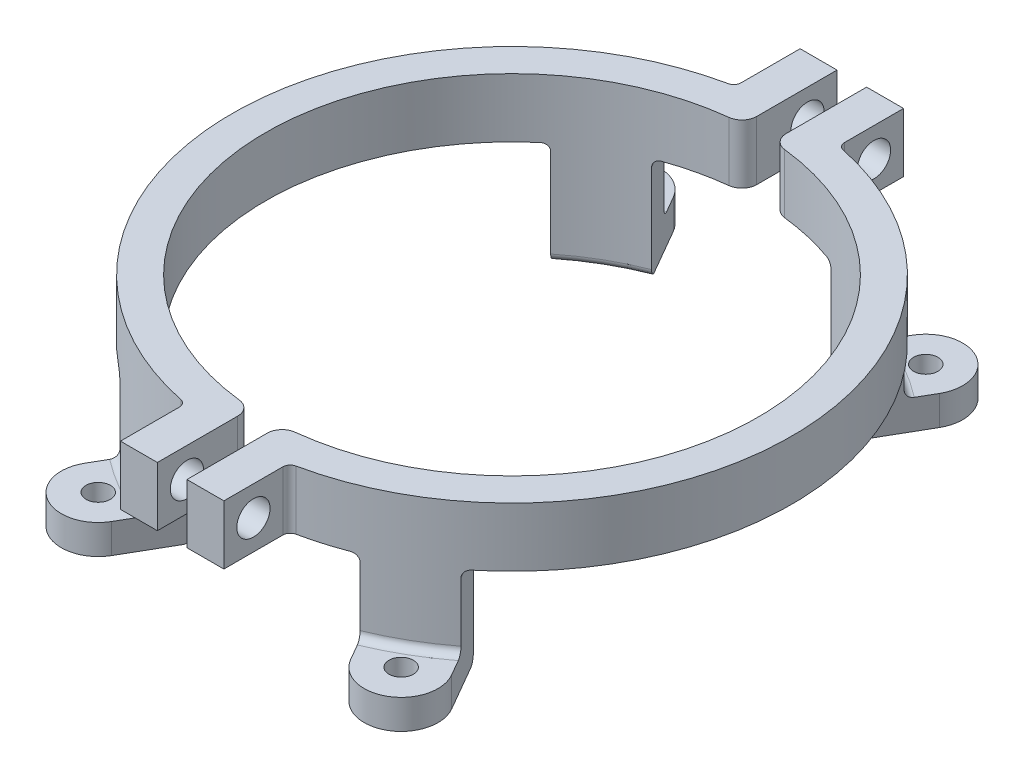
SolidWorks part; units mm, degrees
material "尼龙 101"
ref_plane "前视基准面" through (0, 0, 0) normal (0, 0, 1) x (1, 0, 0)
ref_plane "上视基准面" through (0, 0, 0) normal (0, 1, 0) x (1, 0, 0)
ref_plane "右视基准面" through (0, 0, 0) normal (1, 0, 0) x (0, 0, -1)
sketch "草图1" plane through (0, 0, 0) normal (0, 1, 0) x (1, 0, 0)
  line L0 (-7, 38.0174) -> (-7, 46)
  line L1 (-7, 46) -> (-2, 46)
  line L2 (-2, 46) -> (-2, 35.123)
  line L3 (0, 302.7374) -> (0, 0) construction
  line L4 (0, 0) -> (88.0006, 0) construction
  line L8 (2, 46) -> (2, 35.123)
  line L9 (7, 46) -> (2, 46)
  line L10 (7, 38.0174) -> (7, 46)
  line L11 (7, -38.0174) -> (7, -46)
  line L12 (7, -46) -> (2, -46)
  line L13 (2, -46) -> (2, -35.123)
  line L14 (-20.5, 35.507) -> (0, 0) construction
  line L15 (-2, -46) -> (-2, -35.123)
  line L16 (-7, -46) -> (-2, -46)
  line L17 (-7, -38.0174) -> (-7, -46)
  line L18 (-16.1699, 38.007) -> (-14.429, 34.9918)
  line L19 (-24.8301, 33.007) -> (-23.0893, 29.9918)
  line L20 (24.8301, 33.007) -> (23.0893, 29.9918)
  line L21 (16.1699, 38.007) -> (14.429, 34.9918)
  line L22 (-24.8301, -33.007) -> (-23.0893, -29.9918)
  line L23 (-16.1699, -38.007) -> (-14.429, -34.9918)
  line L24 (24.8301, -33.007) -> (23.0893, -29.9918)
  line L25 (16.1699, -38.007) -> (14.429, -34.9918)
  arc A0 (-3.7737, 33.1358) -> (-3.7737, -33.1358) centre (0, 0) ccw
  arc A1 (-23.0893, 29.9918) -> (-23.0893, -29.9918) centre (0, 0) ccw
  arc A2 (-24.8301, 33.007) -> (-16.1699, 38.007) centre (-20.5, 35.507) cw
  arc A4 (-7.7941, 37.0388) -> (-14.429, 34.9918) centre (0, 0) ccw
  arc A7 (-3.7737, 33.1358) -> (-2, 35.123) centre (-4, 35.123) ccw
  arc A8 (-7.7941, 37.0388) -> (-7, 38.0174) centre (-8, 38.0174) ccw
  arc A9 (7.7941, 37.0388) -> (7, 38.0174) centre (8, 38.0174) cw
  arc A10 (3.7737, 33.1358) -> (2, 35.123) centre (4, 35.123) cw
  arc A14 (24.8301, 33.007) -> (16.1699, 38.007) centre (20.5, 35.507) ccw
  arc A15 (14.429, 34.9918) -> (7.7941, 37.0388) centre (0, 0) ccw
  arc A16 (24.8301, -33.007) -> (16.1699, -38.007) centre (20.5, -35.507) cw
  arc A23 (-24.8301, -33.007) -> (-16.1699, -38.007) centre (-20.5, -35.507) ccw
  arc A24 (3.7737, -33.1358) -> (2, -35.123) centre (4, -35.123) ccw
  arc A25 (7.7941, -37.0388) -> (7, -38.0174) centre (8, -38.0174) ccw
  arc A26 (-7.7941, -37.0388) -> (-7, -38.0174) centre (-8, -38.0174) cw
  arc A27 (-3.7737, -33.1358) -> (-2, -35.123) centre (-4, -35.123) cw
  arc A28 (-14.429, -34.9918) -> (-7.7941, -37.0388) centre (0, 0) ccw
  arc A29 (7.7941, -37.0388) -> (14.429, -34.9918) centre (0, 0) ccw
  arc A30 (3.7737, -33.1358) -> (3.7737, 33.1358) centre (0, 0) ccw
  arc A31 (23.0893, -29.9918) -> (23.0893, 29.9918) centre (0, 0) ccw
  dimension "D1" = 66.7
  dimension "D2" = 4.5
  dimension "D6" = 5
  dimension "D10" = 1
  dimension "D12" = 2
  dimension "D3" = 4
  dimension "D4" = 5
  dimension "D8" = 41
  dimension "D9" = 60
  dimension "D11" = 92
extrude "凸台-拉伸1" add sketch "草图1" along normal mid plane 22
delete or keep bodies "实体-删除/保留 1" [suppressed] type delete bodies bodies 109
sketch "草图3" plane through (0, 11, 0) normal (0, 1, 0) x (1, 0, 0)
  line L0 (-16.1699, -38.007) -> (-14.429, -34.9918) construction
  line L1 (-23.0893, -29.9918) -> (-24.8301, -33.007) construction
  line L2 (-16.1699, -38.007) -> (-14.429, -34.9918)
  line L3 (-23.0893, -29.9918) -> (-24.8301, -33.007)
  line L4 (-11.0319, 0) -> (11.0319, 0) construction
  line L5 (-23.0893, 29.9918) -> (-24.8301, 33.007)
  line L6 (-16.1699, 38.007) -> (-14.429, 34.9918)
  line L7 (0, -11.0319) -> (0, 11.0319) construction
  line L8 (16.1699, 38.007) -> (14.429, 34.9918)
  line L9 (23.0893, 29.9918) -> (24.8301, 33.007)
  line L10 (23.0893, -29.9918) -> (24.8301, -33.007)
  line L11 (16.1699, -38.007) -> (14.429, -34.9918)
  arc A2 (-14.429, -34.9918) -> (-7.7941, -37.0388) centre (0, 0) ccw construction
  arc A3 (-23.0893, -29.9918) -> (-14.429, -34.9918) centre (0, 0) ccw
  arc A4 (-24.8301, -33.007) -> (-16.1699, -38.007) centre (-20.5, -35.507) ccw construction
  arc A6 (-24.8301, -33.007) -> (-16.1699, -38.007) centre (-20.5, -35.507) ccw
  arc A8 (-24.8301, 33.007) -> (-16.1699, 38.007) centre (-20.5, 35.507) cw
  arc A9 (-23.0893, 29.9918) -> (-14.429, 34.9918) centre (0, 0) cw
  arc A10 (23.0893, 29.9918) -> (14.429, 34.9918) centre (0, 0) ccw
  arc A11 (24.8301, 33.007) -> (16.1699, 38.007) centre (20.5, 35.507) ccw
  arc A13 (24.8301, -33.007) -> (16.1699, -38.007) centre (20.5, -35.507) cw
  arc A14 (23.0893, -29.9918) -> (14.429, -34.9918) centre (0, 0) cw
extrude "切除-拉伸2" cut sketch "草图3" against normal offset from surface (18 mm away) 4 up to face at (-13.2249, -11, 0)
sketch "草图4" plane through (0, -11, 0) normal (0, -1, 0) x (1, 0, 0)
  line L10 (0, -11.0319) -> (0, 11.0319) construction
  line L11 (20.8167, -26.0555) -> (23.0893, -29.9918)
  line L12 (23.0893, 29.9918) -> (20.8167, 26.0555)
  line L13 (12.1564, 31.0555) -> (14.429, 34.9918)
  line L14 (7, 46) -> (7, 38.0174)
  line L15 (2, 46) -> (7, 46)
  line L16 (2, 35.123) -> (2, 46)
  line L17 (2, -46) -> (2, -35.123)
  line L18 (7, -46) -> (2, -46)
  line L19 (7, -38.0174) -> (7, -46)
  line L20 (-16.1699, -38.007) -> (-14.429, -34.9918)
  line L21 (-7, -38.0174) -> (-7, -46)
  line L22 (-7, -46) -> (-2, -46)
  line L23 (-2, -46) -> (-2, -35.123)
  line L24 (-2, 35.123) -> (-2, 46)
  line L25 (-2, 46) -> (-7, 46)
  line L26 (-7, 46) -> (-7, 38.0174)
  line L27 (-14.429, 34.9918) -> (-16.1699, 38.007)
  line L28 (-24.8301, 33.007) -> (-23.0893, 29.9918)
  line L29 (-23.0893, -29.9918) -> (-24.8301, -33.007)
  line L30 (-14.429, -34.9918) -> (-12.1564, -31.0555)
  line L31 (-7, -38.0174) -> (-7, -46)
  line L32 (-7, -46) -> (-2, -46)
  line L33 (-2, -46) -> (-2, -35.123)
  line L34 (-2, 35.123) -> (-2, 46)
  line L35 (-2, 46) -> (-7, 46)
  line L36 (-7, 46) -> (-7, 38.0174)
  line L37 (-12.1564, 31.0555) -> (-14.429, 34.9918)
  line L38 (-23.0893, 29.9918) -> (-20.8167, 26.0555)
  line L39 (-20.8167, -26.0555) -> (-23.0893, -29.9918)
  line L40 (14.429, -34.9918) -> (12.1564, -31.0555)
  arc A10 (-20.8167, 26.0555) -> (-20.8167, -26.0555) centre (0, 0) ccw
  arc A11 (-12.1564, -31.0555) -> (-3.7737, -33.1358) centre (0, 0) ccw
  arc A12 (23.0893, 29.9918) -> (23.0893, -29.9918) centre (0, 0) cw
  arc A13 (7.7941, 37.0388) -> (14.429, 34.9918) centre (0, 0) cw
  arc A14 (7.7941, 37.0388) -> (7, 38.0174) centre (8, 38.0174) cw
  arc A15 (3.7737, 33.1358) -> (2, 35.123) centre (4, 35.123) cw
  arc A16 (3.7737, 33.1358) -> (12.1564, 31.0555) centre (0, 0) cw
  arc A17 (2, -35.123) -> (3.7737, -33.1358) centre (4, -35.123) cw
  arc A18 (7, -38.0174) -> (7.7941, -37.0388) centre (8, -38.0174) cw
  arc A19 (14.429, -34.9918) -> (7.7941, -37.0388) centre (0, 0) cw
  arc A20 (-24.8301, -33.007) -> (-16.1699, -38.007) centre (-20.5, -35.507) ccw
  arc A21 (-14.429, -34.9918) -> (-7.7941, -37.0388) centre (0, 0) ccw
  arc A22 (-7, -38.0174) -> (-7.7941, -37.0388) centre (-8, -38.0174) ccw
  arc A23 (-2, -35.123) -> (-3.7737, -33.1358) centre (-4, -35.123) ccw
  arc A24 (-3.7737, 33.1358) -> (-3.7737, -33.1358) centre (0, 0) ccw
  arc A25 (-3.7737, 33.1358) -> (-2, 35.123) centre (-4, 35.123) ccw
  arc A26 (-7.7941, 37.0388) -> (-7, 38.0174) centre (-8, 38.0174) ccw
  arc A27 (-7.7941, 37.0388) -> (-14.429, 34.9918) centre (0, 0) ccw
  arc A28 (-16.1699, 38.007) -> (-24.8301, 33.007) centre (-20.5, 35.507) ccw
  arc A29 (-23.0893, 29.9918) -> (-23.0893, -29.9918) centre (0, 0) ccw
  arc A31 (-14.429, -34.9918) -> (-7.7941, -37.0388) centre (0, 0) ccw
  arc A32 (-7, -38.0174) -> (-7.7941, -37.0388) centre (-8, -38.0174) ccw
  arc A33 (-2, -35.123) -> (-3.7737, -33.1358) centre (-4, -35.123) ccw
  arc A34 (-3.7737, 33.1358) -> (-12.1564, 31.0555) centre (0, 0) ccw
  arc A35 (-3.7737, 33.1358) -> (-2, 35.123) centre (-4, 35.123) ccw
  arc A36 (-7.7941, 37.0388) -> (-7, 38.0174) centre (-8, 38.0174) ccw
  arc A37 (-7.7941, 37.0388) -> (-14.429, 34.9918) centre (0, 0) ccw
  arc A39 (-23.0893, 29.9918) -> (-23.0893, -29.9918) centre (0, 0) ccw
  arc A40 (12.1564, -31.0555) -> (3.7737, -33.1358) centre (0, 0) cw
  arc A41 (20.8167, 26.0555) -> (20.8167, -26.0555) centre (0, 0) cw
  dimension "D1" = 0
extrude "切除-拉伸3" cut sketch "草图4" against normal offset from surface (14 mm away) 8 up to face at (-9.8052, 11, 0)
sketch "草图2" plane through (0, 0, 0) normal (1, 0, 0) x (0, 0, -1)
  line L0 (0, 0) -> (0, 11) construction
  line L1 (37.0388, 11) -> (-37.0388, 11) construction
  line L2 (-46, 11) -> (-46, 3) construction
  line L3 (-46, 11) -> (-46, 3) construction
  circle A0 centre (-42, 7) radius 2.25
  circle A1 centre (42, 7) radius 2.25
  point P14 (-46, 7)
  dimension "D1" = 4.5
  dimension "D2" = 4
extrude "切除-拉伸1" cut sketch "草图2" against normal through all both and the other way through all
hole_wizard "M4 螺纹孔1" positions "草图5" profile "草图6" tap size "M4" standard "GB" end condition through all
sketch "草图5" plane through (0, -11, 0) normal (0, -1, 0) x (-1, 0, 0)
  point P0 (-20.5, 35.507)
  point P3 (-20.5, -35.507)
  point P6 (20.5, 35.507)
  point P9 (20.5, -35.507)
sketch "草图6" plane through (20.5, -11, -35.507) normal (1, 0, 0) x (0, 0, -1)
  line L0 (0, 0) -> (0, 22)
  line L1 (0, 22) -> (1.65, 22)
  line L2 (1.65, 22) -> (1.65, 0)
  line L5 (1.65, 0) -> (0, 0)
  line L11 (0, -6.35) -> (0, 107.95) construction
  dimension "通孔螺纹孔钻头直径" = 3.3
  dimension "通孔螺纹孔钻头深度" = 22
cosmetic thread "孔螺蚊线1" parameters "D2"=4
cosmetic thread "孔螺蚊线2" parameters "D2"=4
cosmetic thread "孔螺蚊线3" parameters "D2"=4
cosmetic thread "孔螺蚊线4" parameters "D2"=4
fillet "圆角1" radius 1 6 edges at (16.675, -11, 28.8819) (16.675, -11, -28.8819) (13.2927, 3, 33.0237) (21.953, 3, 28.0237) (21.953, 3, -28.0237) (13.2927, 3, -33.0237)
fillet "圆角2" radius 1 6 edges at (-16.675, -11, -28.8819) (-21.953, 3, -28.0237) (-13.2927, 3, -33.0237) (-16.675, -11, 28.8819) (-21.953, 3, 28.0237) (-13.2927, 3, 33.0237)
fillet "圆角3" radius 1 2 edges at (-18.925, -7, 32.7791) (-18.925, -7, -32.7791)
fillet "圆角4" radius 1 2 edges at (18.925, -7, -32.7791) (18.925, -7, 32.7791)
sketch "草图7" plane through (0, 11, 0) normal (0, 1, 0) x (1, 0, 0)
  line L0 (-42, 0) -> (0, 0) construction
  line L1 (0, 0) -> (-29.6985, 29.6985) construction
  line L2 (-32.1734, 27.2236) -> (-29.1242, 24.1744)
  line L3 (-27.2236, 32.1734) -> (-24.1744, 29.1242)
  line L4 (0, -11.0319) -> (0, 11.0319) construction
  line L5 (27.2236, 32.1734) -> (24.1744, 29.1242)
  line L6 (32.1734, 27.2236) -> (29.1242, 24.1744)
  line L7 (-11.0319, 0) -> (11.0319, 0) construction
  line L8 (-27.2236, -32.1734) -> (-24.1744, -29.1242)
  line L9 (-32.1734, -27.2236) -> (-29.1242, -24.1744)
  line L10 (27.2236, -32.1734) -> (24.1744, -29.1242)
  line L11 (32.1734, -27.2236) -> (29.1242, -24.1744)
  circle A0 centre (0, 0) radius 42 construction
  circle A2 centre (-29.6985, 29.6985) radius 3.5
  arc A4 (-7.7941, 37.0388) -> (-7.7941, -37.0388) centre (0, 0) ccw construction
  circle A5 centre (0, 0) radius 37.85
  circle A6 centre (29.6985, 29.6985) radius 3.5
  circle A7 centre (-29.6985, -29.6985) radius 3.5
  circle A8 centre (29.6985, -29.6985) radius 3.5
  arc M2 (7.7941, -37.0388) -> (7.7941, 37.0388) centre (0, 0) ccw
  dimension "D1" = 84
  dimension "D3" = 7
  dimension "D2" = 45
extrude "凸台-拉伸2" [suppressed] add sketch "草图7" against normal blind 4 contours A6 | L6 A6 L5 M2 | A8 | A8 L11 L10 M2 | A7 | L9 A7 L8 A5 | A2 | A5 L3 A2 L2
sketch "草图12" [suppressed] plane through (0, 7.2, 0) normal (0, 1, 0) x (1, 0, 0)
  circle A0 centre (29.6985, -29.6985) radius 3.5
  circle A1 centre (-29.6985, -29.6985) radius 3.5
  circle A2 centre (-29.6985, 29.6985) radius 3.5
  circle A3 centre (29.6985, 29.6985) radius 3.5
  point P13 (0, 0)
  dimension "D1" = 4
extrude "凸台-拉伸3" [suppressed] add sketch "草图12" along normal blind 0.5
chamfer "倒角1" [suppressed] distance 0.5 angle 45
chamfer "倒角2" [suppressed] distance 0.5 angle 45
fillet "圆角5" [suppressed] radius 1
fillet "圆角6" [suppressed] radius 1
hole_wizard "M3 螺纹孔3" [suppressed] positions "草图13" profile "草图14" tap size "M3" standard "GB"
sketch "草图13" [suppressed] plane through (0, 7, 0) normal (0, 1, 0) x (1, 0, 0)
  point P0 (-29.6985, 29.6985)
  point P3 (29.6985, 29.6985)
  point P6 (29.6985, -29.6985)
  point P9 (-29.6985, -29.6985)
sketch "草图14" plane through (-29.6985, 7, -29.6985) normal (1, 0, 0) x (0, 0, 1)
  line L0 (0, 0) -> (0, 13.5574)
  line L1 (0, 13.5574) -> (1.25, 13.5574)
  line L2 (1.25, 13.5574) -> (1.25, 0)
  line L5 (1.25, 0) -> (0, 0)
  line L11 (0, -6.35) -> (0, 107.95) construction
  dimension "通孔螺纹孔钻头直径" = 2.5
  dimension "通孔螺纹孔钻头深度" = 13.5574
cosmetic thread "孔螺蚊线10" parameters "D2"=3
cosmetic thread "孔螺蚊线11" parameters "D2"=3
cosmetic thread "孔螺蚊线12" parameters "D2"=3
cosmetic thread "孔螺蚊线13" parameters "D2"=3
hole_wizard "M3 螺纹孔4" [suppressed] positions "草图15" profile "草图16" tap size "M3" standard "GB"
sketch "草图15" [suppressed] plane through (0, 7.2, 0) normal (0, 1, 0) x (1, 0, 0)
  point P0 (-29.6985, 29.6985)
  point P3 (29.6985, 29.6985)
  point P6 (29.6985, -29.6985)
  point P9 (-29.6985, -29.6985)
sketch "草图16" plane through (-29.6985, 7.2, -29.6985) normal (1, 0, 0) x (0, 0, 1)
  line L0 (0, 0) -> (0, 14.4574)
  line L1 (0, 14.4574) -> (1.25, 14.4574)
  line L2 (1.25, 14.4574) -> (1.25, 0)
  line L5 (1.25, 0) -> (0, 0)
  line L11 (0, -6.35) -> (0, 107.95) construction
  dimension "通孔螺纹孔钻头直径" = 2.5
  dimension "通孔螺纹孔钻头深度" = 14.4574
cosmetic thread "孔螺蚊线14" parameters "D2"=3
cosmetic thread "孔螺蚊线15" parameters "D2"=3
cosmetic thread "孔螺蚊线16" parameters "D2"=3
cosmetic thread "孔螺蚊线17" parameters "D2"=3
sketch "草图17" plane through (0, 0, 0) normal (1, 0, 0) x (0, 0, -1)
  line L0 (-46.0106, 0) -> (51.0678, 0) construction
  line L2 (-50, 25) -> (50, 25)
  line L3 (-50, 25) -> (-50, -25)
  line L4 (-50, -25) -> (50, -25)
  line L5 (50, 25) -> (50, -25)
  line L6 (-50, 25) -> (50, -25) construction
  line L7 (-50, -25) -> (50, 25) construction
  point P3 (0, 0)
  dimension "D1" = 100
  dimension "D2" = 50
split "分割1" trim tools "草图17" bodies to split 115 resulting bodies 129
